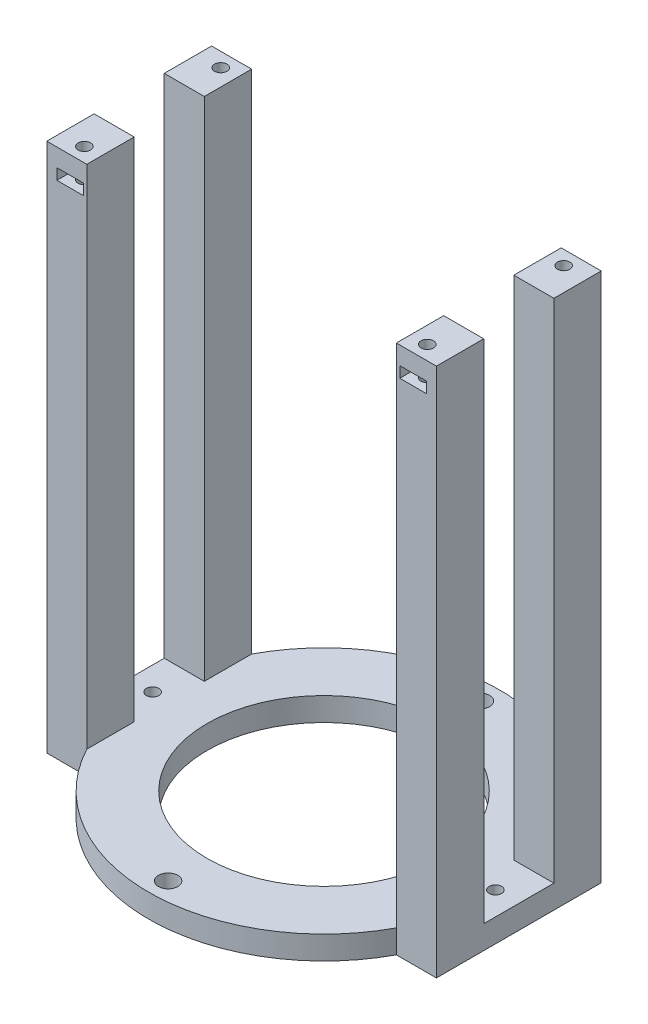
SolidWorks part; units mm, degrees
ref_plane "Front Plane" through (0, 0, 0) normal (0, 0, 1) x (1, 0, 0)
ref_plane "Top Plane" through (0, 0, 0) normal (0, 1, 0) x (1, 0, 0)
ref_plane "Right Plane" through (0, 0, 0) normal (1, 0, 0) x (0, 0, -1)
sketch "Sketch1" plane through (0, 0, 0) normal (0, 1, 0) x (1, 0, 0)
  line L0 (33, 0) -> (-33, 0) construction
  line L2 (-16, 21.15) -> (-50, 21.15)
  line L3 (-16, 21.15) -> (-16, -21.15)
  line L4 (-16, -21.15) -> (-50, -21.15)
  line L5 (-50, 21.15) -> (-50, -21.15)
  line L6 (-16, 21.15) -> (-50, -21.15) construction
  line L7 (-16, -21.15) -> (-50, 21.15) construction
  line L8 (16, 21.15) -> (50, 21.15)
  line L9 (16, 21.15) -> (16, -21.15)
  line L10 (16, -21.15) -> (50, -21.15)
  line L11 (50, 21.15) -> (50, -21.15)
  line L12 (16, 21.15) -> (50, -21.15) construction
  line L13 (16, -21.15) -> (50, 21.15) construction
  circle A0 centre (0, 0) radius 45
  point P6 (0, 0)
  dimension "D1" = 90
  dimension "D2" = 66
  dimension "D3" = 42.3
  dimension "D4" = 42.3
  dimension "D5" = 34
  dimension "D6" = 34
extrude "body" add sketch "Sketch1" along normal blind 6 contours A0 L2 L5 L4 | L2 A0 L4 L3 | L8 A0 L2 L3 L4 L10 L9 | L10 A0 L8 L9 | A0 L10 L11 L8 region at (-29.6863, 0, 0) region at (0, 0, 0) region at (-46.4607, 0, 0) region at (29.6863, 0, 0) region at (46.4607, 0, 0)
sketch "Sketch2" plane through (0, 6, 0) normal (0, 1, 0) x (1, 0, 0)
  line L1 (-50, 21.15) -> (-39.72, 21.15)
  line L2 (-50, 21.15) -> (-50, -21.15)
  line L3 (-50, -21.15) -> (-39.72, -21.15)
  line L4 (-39.72, 21.15) -> (-39.72, -21.15)
  line L5 (50, 21.15) -> (39.72, 21.15)
  line L6 (50, 21.15) -> (50, -21.15)
  line L7 (50, -21.15) -> (39.72, -21.15)
  line L8 (39.72, 21.15) -> (39.72, -21.15)
  line M6 (39.72, -21.15) -> (50, -21.15)
  line M7 (50, -21.15) -> (50, 21.15)
  line M8 (50, 21.15) -> (39.72, 21.15)
extrude "wings" add sketch "Sketch2" along normal blind 130 contours L8 M8 M6 M7 | L2 L1 L4 L3 region at (44.86, 6, 0)
sketch "Sketch3" plane through (0, 136, 0) normal (0, 1, 0) x (1, 0, 0)
  line L0 (44, 0) -> (-44, 0) construction
  line L1 (44, -17.5) -> (44, 17.5) construction
  line L2 (-44, -17.5) -> (-44, 17.5) construction
  circle A0 centre (44, -17.5) radius 1.6
  circle A1 centre (-44, -17.5) radius 1.6
  circle A2 centre (-44, 17.5) radius 1.6
  circle A3 centre (44, 17.5) radius 1.6
  point P4 (0, 0)
  point P8 (44, 0)
  point P11 (-44, 0)
  dimension "D4" = 3.2
  dimension "D5" = 3.2
  dimension "D6" = 3.2
  dimension "D7" = 3.2
  dimension "D1" = 88
  dimension "D2" = 35
  dimension "D3" = 35
extrude "mounting-bore" cut sketch "Sketch3" against normal through all
sketch "Sketch5" plane through (50, 0, 0) normal (1, 0, 0) x (0, 0, -1)
  line L0 (0, 0) -> (0, 6)
  line L1 (21.15, 0) -> (-21.15, 0) construction
  line L2 (9, 6) -> (-9, 6)
  line L3 (9, 6) -> (-9, 6)
  line L4 (9, 6) -> (9, 136)
  line L5 (-9, 6) -> (-9, 136)
  line L6 (9, 136) -> (-9, 136)
  point P7 (0, 6)
  line M9 (21.15, 136) -> (-21.15, 136)
  dimension "D1" = 6
  dimension "D2" = 18
  dimension "D3" = 130
extrude "cut-excess-material" cut sketch "Sketch5" against normal through all contours L5 L2 L4 M9 region at (50, 71, 0)
sketch "Sketch6" plane through (0, 0, 0) normal (0, -1, 0) x (1, 0, 0)
  line L0 (-44, 0) -> (44, 0)
  circle A0 centre (-44, 0) radius 1.6
  circle A1 centre (44, 0) radius 1.6
  point P4 (0, 0)
  dimension "D2" = 3.2
  dimension "D3" = 3.2
  dimension "D1" = 88
extrude "cut-battery-mount" cut sketch "Sketch6" against normal up to next contours A0 | A1 region at (44, 0, 1.5547) region at (-45.5547, 0, 0)
sketch "Sketch8" plane through (0, 0, 21.15) normal (0, 0, 1) x (1, 0, 0)
  line L0 (39.72, 136) -> (44, 136)
  line L1 (39.72, 136) -> (50, 136) construction
  line L2 (44, 136) -> (44, 130)
  line L4 (40.6, 131.4) -> (47.4, 131.4)
  line L5 (40.6, 131.4) -> (40.6, 128.6)
  line L6 (40.6, 128.6) -> (47.4, 128.6)
  line L7 (47.4, 131.4) -> (47.4, 128.6)
  line L8 (40.6, 131.4) -> (47.4, 128.6) construction
  line L9 (40.6, 128.6) -> (47.4, 131.4) construction
  dimension "D1" = 4.28
  dimension "D2" = 6
  dimension "D3" = 6.8
  dimension "D4" = 2.8
extrude "capture-nut-1" cut sketch "Sketch8" against normal blind 7.3 contours L5 L4 L7 L6
pattern_circular "CirPattern1" count 2 over 360 about axis through (0, 6, 0) along (0, 1, 0) of "capture-nut-1"
sketch "Sketch10" plane through (0, 0, -21.15) normal (0, 0, -1) x (-1, 0, 0)
  line L0 (-39.72, 136) -> (-44, 136)
  line L1 (-50, 136) -> (-39.72, 136) construction
  line L2 (-44, 136) -> (-44, 130)
  line L4 (-47.4, 131.4) -> (-40.6, 131.4)
  line L5 (-47.4, 131.4) -> (-47.4, 128.6)
  line L6 (-47.4, 128.6) -> (-40.6, 128.6)
  line L7 (-40.6, 131.4) -> (-40.6, 128.6)
  line L8 (-47.4, 131.4) -> (-40.6, 128.6) construction
  line L9 (-47.4, 128.6) -> (-40.6, 131.4) construction
  dimension "D1" = 4.28
  dimension "D2" = 6
  dimension "D3" = 6.8
  dimension "D4" = 2.8
extrude "capture-nut-2" cut sketch "Sketch10" against normal blind 7.3 contours L7 L4 L5 L6 region at (45.7, 131.3265, -21.15)
pattern_circular "CirPattern2" count 2 over 360 about axis through (0, 6, 0) along (0, 1, 0) of "capture-nut-2"
sketch "Sketch11" plane through (0, 0, 0) normal (0, -1, 0) x (1, 0, 0)
  circle A0 centre (0, 0) radius 30
  dimension "D1" = 60
extrude "cut-center-hole" cut sketch "Sketch11" against normal up to next
sketch "Sketch12" plane through (0, 0, 0) normal (0, -1, 0) x (1, 0, 0)
  line L0 (0, 40) -> (0, -40)
  circle A0 centre (0, -40) radius 2.5
  circle A1 centre (0, 40) radius 2.5
  point P5 (0, 0)
  dimension "D2" = 5
  dimension "D3" = 5
  dimension "D1" = 80
extrude "cut-harness-mount" cut sketch "Sketch12" against normal up to next contours A1 | A0 region at (1.7178, 0, -38.2822) region at (-1.7178, 0, 41.7178)
equation "\"th\"= 6mm"
equation "\"D1@body\"=\"th\""
equation "\"wing\" = 130mm"
equation "\"D1@wings\"=\"wing\""
equation "\"D1@Sketch5\"=\"th\""
equation "\"D3@Sketch5\"=\"wing\""
equation "\"capture_nut_depth\"= 7.3mm"
equation "\"capture_nut_height\"= 2.8mm"
equation "\"capture_nut_width\"= 6.8mm"
equation "\"D3@Sketch8\"=\"capture_nut_width\""
equation "\"D4@Sketch8\"=\"capture_nut_height\""
equation "\"D1@capture-nut-1\" = \"capture_nut_depth\""
equation "\"D3@Sketch10\"=\"capture_nut_width\""
equation "\"D4@Sketch10\"=\"capture_nut_height\""
equation "\"D1@capture-nut-2\" = \"capture_nut_depth\""
